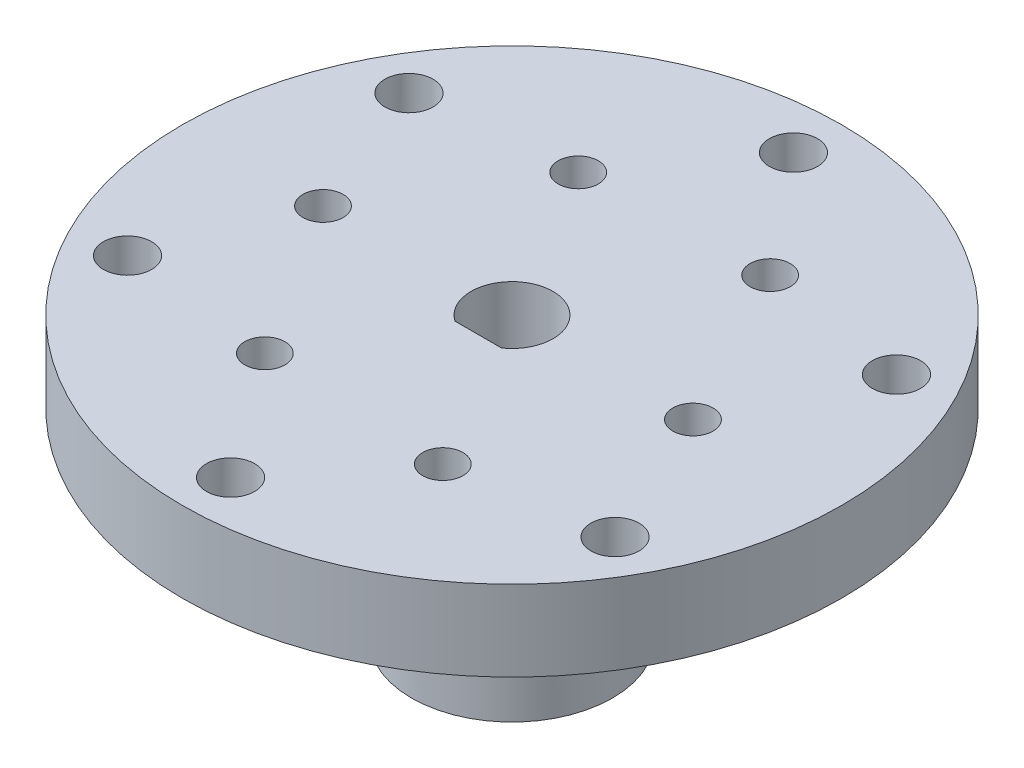
SolidWorks part; units mm, degrees
material "6061 Alloy"
ref_plane "Front Plane" through (0, 0, 0) normal (0, 0, 1) x (1, 0, 0)
ref_plane "Top Plane" through (0, 0, 0) normal (0, 1, 0) x (1, 0, 0)
ref_plane "Right Plane" through (0, 0, 0) normal (1, 0, 0) x (0, 0, -1)
sketch "Sketch1" plane through (0, 0, 0) normal (0, 1, 0) x (1, 0, 0)
  circle A0 centre (0, 0) radius 5.1
  circle A1 centre (0, 0) radius 12.5
  dimension "D1" = 10.2
  dimension "D2" = 25
extrude "Boss-Extrude1" add sketch "Sketch1" along normal blind 15
sketch "Sketch2" plane through (0, 15, 0) normal (0, 1, 0) x (1, 0, 0)
  circle A0 centre (0, 0) radius 5.1
  circle A1 centre (0, 0) radius 41
  circle A3 centre (0, 0) radius 5.1 construction
  dimension "D1" = 82
extrude "Boss-Extrude2" add sketch "Sketch2" along normal blind 20
sketch "Sketch3" plane through (0, 35, 0) normal (0, 1, 0) x (1, 0, 0)
  circle A0 centre (0, 0) radius 35 construction
  circle A1 centre (0, 35) radius 3
  circle A2 centre (30.3109, 17.5) radius 3
  circle A3 centre (30.3109, -17.5) radius 3
  circle A4 centre (0, -35) radius 3
  circle A5 centre (-30.3109, -17.5) radius 3
  circle A6 centre (-30.3109, 17.5) radius 3
  point P17 (0, 0)
  dimension "D1" = 70
  dimension "D2" = 6
  dimension "D3" = 6
extrude "Cut-Extrude1" cut sketch "Sketch3" against normal through all
sketch "Sketch4" plane through (0, 0, 0) normal (0, -1, 0) x (1, 0, 0)
  line L0 (-2.8931, 4.2) -> (2.8931, 4.2)
  circle A0 centre (0, 0) radius 5.1
  circle A1 centre (0, 0) radius 5.1 construction
  circle M3 centre (0, 0) radius 5.1
  dimension "D1" = 4.2
extrude "Boss-Extrude3" add sketch "Sketch4" against normal blind 35 contours L0 M3 region at (0, 0, 4.5629)
sketch "Sketch5" plane through (0, 0, 4.2) normal (0, 0, -1) x (-1, 0, 0)
  line L0 (0, 35) -> (0, 0) construction
  line L1 (2.8931, 35) -> (-2.8931, 35) construction
  line L2 (2.8931, 0) -> (-2.8931, 0) construction
  circle A0 centre (0, 9) radius 1.5
  dimension "D1" = 3
  dimension "D2" = 9
extrude "Cut-Extrude2" cut sketch "Sketch5" against normal through all and the other way through all
sketch "Sketch6" plane through (0, 15, 0) normal (0, -1, 0) x (1, 0, 0)
  circle A0 centre (0, 0) radius 12.5
  circle A1 centre (0, 0) radius 41
  circle A2 centre (0, 0) radius 41 construction
  circle A3 centre (0, 0) radius 12.5 construction
extrude "Cut-Extrude3" cut sketch "Sketch6" against normal blind 10
sketch "Sketch7" plane through (0, 35, 0) normal (0, 1, 0) x (1, 0, 0)
  circle A0 centre (-2.8931, -4.2) radius 0.7109
  circle A1 centre (2.8931, -4.2) radius 0.682
sketch "Sketch8" plane through (0, 0, 0) normal (0, -1, 0) x (1, 0, 0)
  circle A0 centre (0, 0) radius 22.5 construction
  circle A1 centre (22.5, 0) radius 2.5
  circle A2 centre (0, 0) radius 23.5 construction
  circle A3 centre (-23.5, 0) radius 2.5
  circle A4 centre (-11.25, -19.4856) radius 2.5
  circle A5 centre (-11.25, 19.4856) radius 2.5
  circle A6 centre (11.75, 20.3516) radius 2.5
  circle A7 centre (11.75, -20.3516) radius 2.5
  point P14 (0, 0)
  point P19 (0, 0)
  dimension "D1" = 45
  dimension "D2" = 1
  dimension "D3" = 5
  dimension "D4" = 5
  dimension "D5" = 3
  dimension "D6" = 3
extrude "Cut-Extrude4" cut sketch "Sketch8" against normal through all
